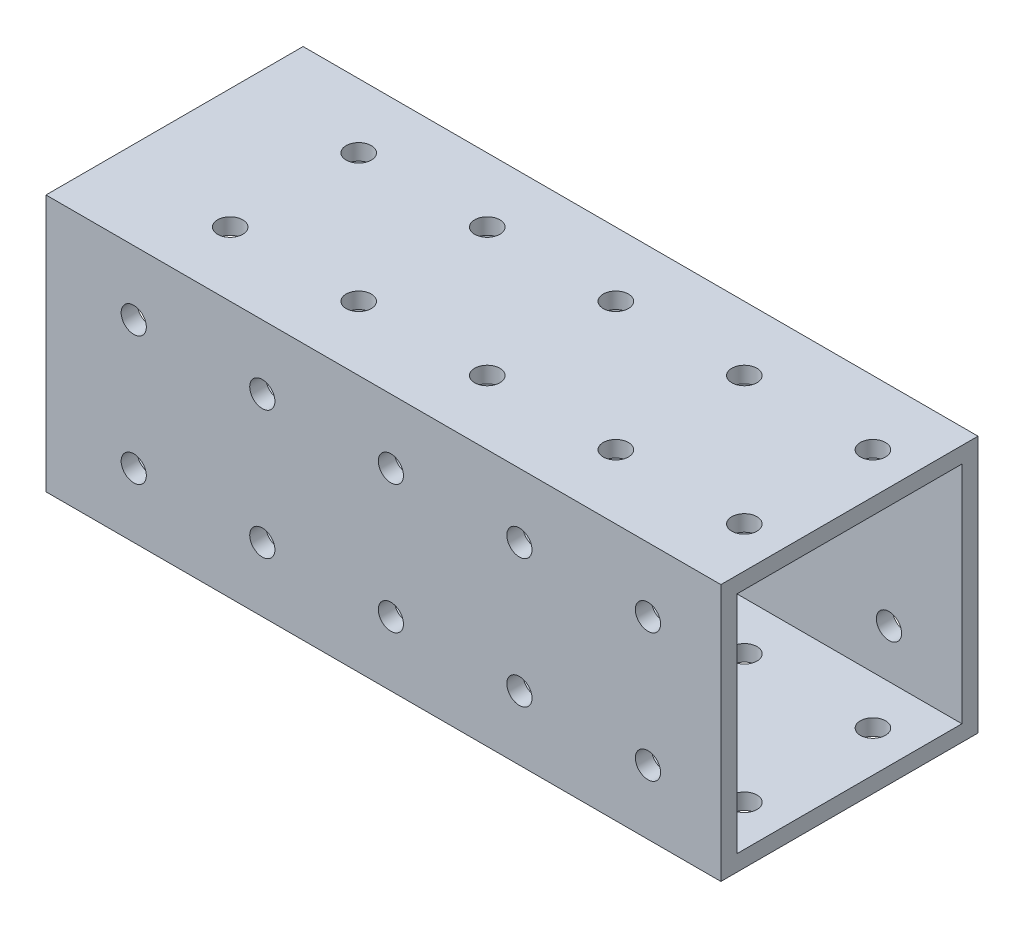
SolidWorks part; units mm, degrees
material "6061-T6 (SS)"
ref_plane "Front Plane" through (0, 0, 0) normal (0, 0, 1) x (1, 0, 0)
ref_plane "Top Plane" through (0, 0, 0) normal (0, 1, 0) x (1, 0, 0)
ref_plane "Right Plane" through (0, 0, 0) normal (1, 0, 0) x (0, 0, -1)
sketch "Sketch1" plane through (0, 0, 0) normal (1, 0, 0) x (0, 0, -1)
  line L1 (0, 0) -> (50.8, 0)
  line L2 (0, 0) -> (0, 50.8)
  line L3 (0, 50.8) -> (50.8, 50.8)
  line L4 (50.8, 0) -> (50.8, 50.8)
  dimension "D1" = 50.8
extrude "Boss-Extrude1" add sketch "Sketch1" along normal blind 133.35
shell "Shell1" thickness 3.175 removed face at (0, 25.4, -25.4) removed face at (133.35, 25.4, -25.4)
sketch "Sketch2" plane through (0, 0, -50.8) normal (0, 0, -1) x (-1, 0, 0)
  circle A0 centre (-118.9383, 38.1) radius 2.4892 construction
  circle A1 centre (-93.5383, 38.1) radius 2.4892 construction
  circle A2 centre (-68.1383, 38.1) radius 2.4892 construction
  circle A3 centre (-42.7383, 38.1) radius 2.4892 construction
  circle A4 centre (-17.3383, 38.1) radius 2.4892 construction
  circle A5 centre (-17.3383, 12.7) radius 2.4892 construction
  circle A6 centre (-42.7383, 12.7) radius 2.4892 construction
  circle A7 centre (-68.1383, 12.7) radius 2.4892 construction
  circle A8 centre (-93.5383, 12.7) radius 2.4892 construction
  circle A9 centre (-118.9383, 12.7) radius 2.4892 construction
  circle A10 centre (-118.9383, 38.1) radius 2.4892
  circle A11 centre (-93.5383, 38.1) radius 2.4892
  circle A12 centre (-68.1383, 38.1) radius 2.4892
  circle A13 centre (-42.7383, 38.1) radius 2.4892
  circle A14 centre (-17.3383, 38.1) radius 2.4892
  circle A15 centre (-17.3383, 12.7) radius 2.4892
  circle A16 centre (-42.7383, 12.7) radius 2.4892
  circle A17 centre (-68.1383, 12.7) radius 2.4892
  circle A18 centre (-93.5383, 12.7) radius 2.4892
  circle A19 centre (-118.9383, 12.7) radius 2.4892
extrude "Cut-Extrude1" cut sketch "Sketch2" against normal through all
sketch "Sketch3" plane through (0, 0, 0) normal (0, -1, 0) x (1, 0, 0)
  line L1 (125.2883, -38.1) -> (125.2883, -12.7) construction
  line L2 (125.2883, -12.7) -> (125.2883, 12.7) construction
  line L3 (284.0383, 0) -> (-312.8617, 0) construction
  line L4 (133.35, -50.8) -> (0, -50.8) construction
  circle A0 centre (125.2883, -12.7) radius 2.4892
  circle A1 centre (125.2883, -38.1) radius 2.4892
  dimension "D1" = 4.9784
  dimension "D2" = 12.7
  dimension "D3" = 12.7
extrude "Cut-Extrude2" cut sketch "Sketch3" against normal through all
pattern_linear "LPattern1" count 5 spacing 25.4 along (-1, 0, 0) of "Cut-Extrude2"
